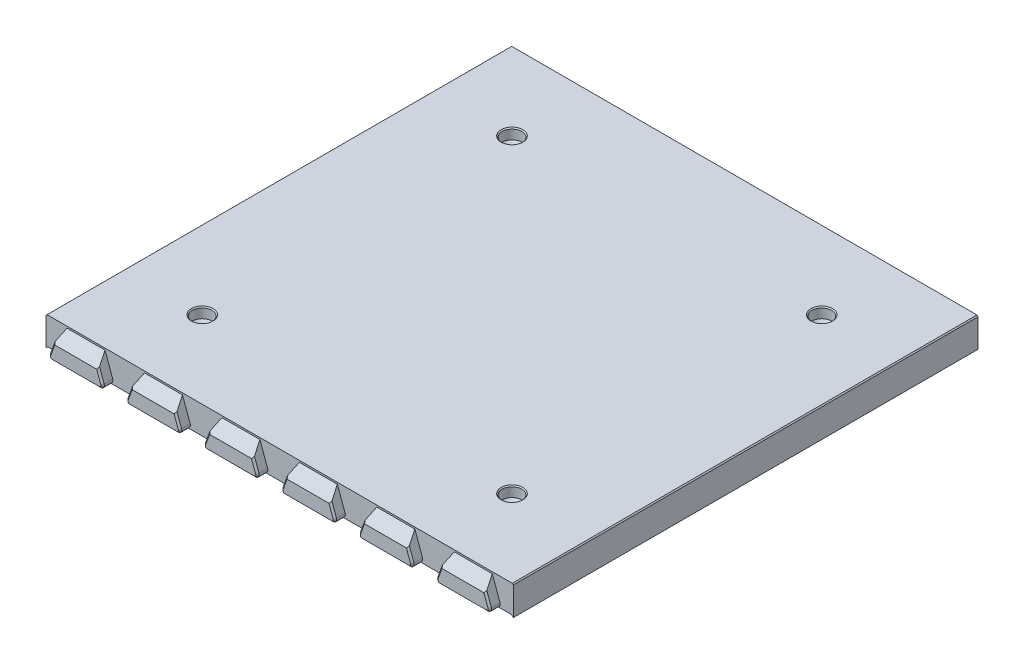
SolidWorks part; units mm, degrees
ref_plane "Front Plane" through (0, 0, 0) normal (0, 0, 1) x (1, 0, 0)
ref_plane "Top Plane" through (0, 0, 0) normal (0, 1, 0) x (1, 0, 0)
ref_plane "Right Plane" through (0, 0, 0) normal (1, 0, 0) x (0, 0, -1)
sketch "Sketch1" plane through (0, 0, 0) normal (0, 0, 1) x (1, 0, 0)
  line L0 (0, 0) -> (0, 8) construction
  line L1 (-67.875, 0) -> (0, 0) construction
  line L2 (-67.875, 0) -> (-67.875, 8)
  line L3 (-67.875, 8) -> (67.875, 8)
  line L5 (-67.875, 0) -> (-65.875, 0)
  line L6 (-65.875, 0) -> (-65.875, 6)
  line L7 (-65.875, 6) -> (65.875, 6)
  line L9 (65.875, 0) -> (65.875, 6)
  line L10 (67.875, 0) -> (65.875, 0)
  line L11 (67.875, 0) -> (67.875, 8)
  point P8 (0, 6)
  dimension "D2" = 6
  dimension "D1" = 67.875
  dimension "D3" = 2
  dimension "D4" = 2
extrude "Boss-Extrude1" add sketch "Sketch1" against normal blind 67.5
sketch "Sketch7" plane through (0, 0, 0) normal (0, 0, 1) x (1, 0, 0)
  line L2 (-65.875, 0) -> (65.875, 0)
  line L13 (-65.875, 0) -> (-65.875, 6)
  line L15 (-65.875, 6) -> (65.875, 6)
  line L16 (65.875, 0) -> (65.875, 6)
  line M3 (-65.875, 0) -> (-65.875, 6)
  line M4 (-65.875, 6) -> (65.875, 6)
  line M5 (65.875, 6) -> (65.875, 0)
extrude "Boss-Extrude7" add sketch "Sketch7" against normal blind 1 contours M4 M3 | M5 region at (0, 3, 0)
sketch "Sketch2" plane through (0, 0, 0) normal (0, 0, 1) x (1, 0, 0)
  line L14 (50.9118, 8) -> (48, 0)
  line L15 (67.875, 8) -> (-67.875, 8) construction
  line L16 (-67.875, 0) -> (67.875, 0) construction
  line L17 (48, 0) -> (64.5, 0)
  line L18 (50.9118, 8) -> (61.5882, 8)
  line L19 (-67.875, 0) -> (67.875, 0) construction
  line L21 (61.5882, 8) -> (64.5, 0)
  line L24 (45, 0) -> (45, 8) construction
  line L27 (28.4118, 8) -> (25.5, 0)
  line L28 (28.4118, 8) -> (39.0882, 8)
  line L29 (25.5, 0) -> (42, 0)
  line L30 (39.0882, 8) -> (42, 0)
  line L31 (5.9118, 8) -> (3, 0)
  line L32 (5.9118, 8) -> (16.5882, 8)
  line L33 (3, 0) -> (19.5, 0)
  line L34 (16.5882, 8) -> (19.5, 0)
  line L35 (-16.5882, 8) -> (-19.5, 0)
  line L36 (-16.5882, 8) -> (-5.9118, 8)
  line L37 (-19.5, 0) -> (-3, 0)
  line L38 (-5.9118, 8) -> (-3, 0)
  line L39 (50.9118, 8) -> (28.4118, 8) construction
  line L40 (67.5, 8) -> (67.5, 0) construction
  line L41 (67.875, 0) -> (67.875, 8) construction
  line L42 (-67.5, 8) -> (-67.5, 0) construction
  line L43 (-67.875, 8) -> (-67.875, 0) construction
  line L44 (-39.0882, 8) -> (-42, 0)
  line L45 (-39.0882, 8) -> (-28.4118, 8)
  line L46 (-42, 0) -> (-25.5, 0)
  line L47 (-28.4118, 8) -> (-25.5, 0)
  line L48 (-61.5882, 8) -> (-64.5, 0)
  line L49 (-61.5882, 8) -> (-50.9118, 8)
  line L50 (-64.5, 0) -> (-48, 0)
  line L51 (-50.9118, 8) -> (-48, 0)
  point P22 (56.25, 8)
  point P23 (33.75, 8)
  dimension "D1" = 70
  dimension "D2" = 0.375
  dimension "D3" = 3
  dimension "D4" = 3
  dimension "D5" = 70
  dimension "D7" = 22.5
  dimension "D8" = 22.5
  dimension "D9" = 0.375
  dimension "D10" = 48
  dimension "D11" = 8
  dimension "D6" = 6
extrude "Boss-Extrude4" add sketch "Sketch2" along normal blind 3
sketch "Sketch8" plane through (0, 0, 0) normal (0, -1, 0) x (1, 0, 0)
  line L0 (-67.875, -22.5) -> (67.875, -22.5) construction
  line L1 (-66.35, -24.7417) -> (-62.65, -23.395)
  line L2 (67.875, -67.5) -> (67.875, 0) construction
  line L3 (-67.875, 0) -> (-64.5, 0) construction
  line L4 (-66.5, -24.9559) -> (-66.5, -20.0441) construction
  line L5 (-66.5, -20.0441) -> (-62.5, -21.5) construction
  line L6 (-62.5, -21.5) -> (-62.5, -23.5) construction
  line L7 (-66.5, -67.5) -> (-66.5, -65.0441) construction
  line L8 (-66.5, -65.0441) -> (-62.5, -66.5) construction
  line L9 (-62.5, -66.5) -> (-62.5, -67.5) construction
  line L10 (-65.875, -67.5) -> (65.875, -67.5) construction
  line L11 (-62.5, -67.5) -> (-66.5, -67.5) construction
  line L12 (-66.5, -24.9559) -> (-62.5, -23.5) construction
  line L13 (0, -67.5) -> (0, 0) construction
  line L22 (-62.65, -21.605) -> (-62.65, -23.395)
  line L23 (-67.875, -67.5) -> (-67.875, 0) construction
  line L28 (-67.875, -67.5) -> (-65.875, -67.5) construction
  line L33 (-66.35, -20.2583) -> (-62.65, -21.605)
  line L34 (-66.35, -24.7417) -> (-66.35, -20.2583)
  line L35 (-66.35, -65.2583) -> (-62.65, -66.605)
  line L36 (-62.65, -66.605) -> (-62.65, -67.35)
  line L37 (-62.65, -67.35) -> (-66.35, -67.35) construction
  line L38 (-66.35, -67.35) -> (-66.35, -65.2583)
  line L39 (-66.35, -67.35) -> (-66.35, -67.5)
  line L40 (-66.35, -67.5) -> (-62.65, -67.5)
  line L41 (-62.65, -67.5) -> (-62.65, -67.35)
  line L42 (66.35, -24.7417) -> (66.35, -20.2583)
  line L43 (66.35, -20.2583) -> (62.65, -21.605)
  line L44 (62.65, -21.605) -> (62.65, -23.395)
  line L45 (66.35, -24.7417) -> (62.65, -23.395)
  line L46 (66.35, -67.5) -> (62.65, -67.5)
  line L47 (66.35, -67.35) -> (66.35, -67.5)
  line L48 (66.35, -67.35) -> (66.35, -65.2583)
  line L49 (66.35, -65.2583) -> (62.65, -66.605)
  line L50 (62.65, -66.605) -> (62.65, -67.35)
  line L51 (62.65, -67.5) -> (62.65, -67.35)
  point P19 (-62.5, -22.5)
  dimension "D1" = 22.5
  dimension "D2" = 0.15
  dimension "D3" = 70
  dimension "D4" = 4
  dimension "D5" = 1.375
  dimension "D6" = 4
  dimension "D7" = 70
  dimension "D8" = 1
  dimension "D9" = 1
  dimension "D10" = 0.15
extrude "Boss-Extrude8" add sketch "Sketch8" against normal up to next and the other way blind 2
chamfer "Chamfer4" distance 0.5 angle 45 14 edges at (64.5, -2, -20.9317) (66.35, -2, -22.5) (64.5, -2, -24.0683) (62.65, -2, -22.5) (-64.5, -2, -20.9317) (-62.65, -2, -22.5) (-64.5, -2, -24.0683) (-66.35, -2, -22.5) (-66.35, -2, -66.3792) (-64.5, -2, -65.9317) (-62.65, -2, -67.0525) (62.65, -2, -67.0525) (64.5, -2, -65.9317) (66.35, -2, -66.3792)
fillet "Fillet4" radius 1 12 edges at (64.5, 0, 1.5) (48, 0, 1.5) (42, 0, 1.5) (25.5, 0, 1.5) (19.5, 0, 1.5) (3, 0, 1.5) (-3, 0, 1.5) (-19.5, 0, 1.5) (-25.5, 0, 1.5) (-42, 0, 1.5) (-48, 0, 1.5) (-64.5, 0, 1.5)
chamfer "Chamfer6" distance 0.5 angle 45 30 edges at (49.7001, 4.671, 3) (62.7999, 4.671, 3) (56.25, 0, 3) (-17.7999, 4.671, 3) (-11.25, 0, 3) (-4.7001, 4.671, 3) (4.7001, 4.671, 3) (11.25, 0, 3) (17.7999, 4.671, 3) (27.2001, 4.671, 3) (40.2999, 4.671, 3) (33.75, 0, 3) (-62.7999, 4.671, 3) (-56.25, 0, 3) (-49.7001, 4.671, 3) (-40.2999, 4.671, 3) (-27.2001, 4.671, 3) (-33.75, 0, 3) (-63.891, 0.4264, 3) (-48.609, 0.4264, 3) (-41.391, 0.4264, 3) (-26.109, 0.4264, 3) (-18.891, 0.4264, 3) (-3.609, 0.4264, 3) (3.609, 0.4264, 3) (18.891, 0.4264, 3) (26.109, 0.4264, 3) (41.391, 0.4264, 3) (48.609, 0.4264, 3) (63.891, 0.4264, 3)
fillet "Fillet2" radius 2 23 edges at (0, 6, -1) (-65.875, 3, -1) (65.875, 6, -10.7156) (65.875, 3, -1) (-65.875, 6, -10.7156) (-64.2625, 6, -23.9819) (-65.875, 3, -24.5688) (-64.2625, 6, -21.0181) (62.65, 6, -22.5) (64.2625, 6, -21.0181) (65.875, 3, -20.4312) (65.875, 3, -24.5688) (64.2625, 6, -23.9819) (62.65, 6, -67.0525) (65.875, 3, -65.4312) (64.2625, 6, -66.0181) (65.875, 6, -45) (-62.65, 6, -67.0525) (-64.2625, 6, -66.0181) (-65.875, 3, -65.4312) (-65.875, 6, -45) (-62.65, 6, -22.5) (-65.875, 3, -20.4312)
mirror "Mirror2" about plane through (0, 0, -67.5) normal (0, 0, 1) of "Fillet4", "Boss-Extrude1", "Boss-Extrude7", "Boss-Extrude4", "Boss-Extrude8", "Chamfer4", "Fillet2", "Chamfer6"
sketch "Sketch9" plane through (0, 0, 0) normal (0, 1, 0) x (1, 0, 0)
  line L16 (-45, 22.5) -> (45, 22.5) construction
  line L17 (-67.875, 67.5) -> (67.875, 67.5) construction
  line L20 (67.875, 135) -> (67.875, 0) construction
  line L24 (0, 22.5) -> (0, 67.5) construction
  line L25 (-67.875, 135) -> (-67.875, 0) construction
  circle A0 centre (-45, 22.5) radius 5
  circle A1 centre (45, 22.5) radius 5
  circle A4 centre (45, 112.5) radius 5
  circle A5 centre (-45, 112.5) radius 5
  point P23 (0, 67.5)
  point P24 (0, 67.5)
  dimension "D3" = 10
  dimension "D1" = 45
  dimension "D2" = 90
extrude "Boss-Extrude9" add sketch "Sketch9" along normal up to next
fillet "Fillet3" radius 3 4 edges at (45, 6, -27.5) (-45, 6, -27.5) (45, 6, -117.5) (-45, 6, -117.5)
sketch "Sketch10" plane through (0, 0, 0) normal (0, 1, 0) x (1, 0, 0)
  circle A0 centre (-45, 112.5) radius 1.85
  circle A1 centre (-45, 22.5) radius 1.85
  circle A2 centre (45, 22.5) radius 1.85
  circle A3 centre (45, 112.5) radius 1.85
  circle A4 centre (-45, 22.5) radius 5 construction
  circle A5 centre (45, 22.5) radius 5 construction
  circle A8 centre (-45, 22.5) radius 5 construction
  circle A9 centre (45, 22.5) radius 5 construction
  dimension "D1" = 3.7
extrude "Cut-Extrude2" cut sketch "Sketch10" along normal through all
sketch "Sketch11" plane through (0, 8, 0) normal (0, 1, 0) x (1, 0, 0)
  circle A0 centre (-45, 112.5) radius 2.85
  circle A1 centre (45, 112.5) radius 2.85
  circle A2 centre (45, 22.5) radius 2.85
  circle A3 centre (-45, 22.5) radius 2.85
  dimension "D1" = 5.7
extrude "Cut-Extrude3" cut sketch "Sketch11" against normal blind 3
chamfer "Chamfer7" distance 1 angle 45 4 edges at (45, 5, -110.65) (-45, 5, -110.65) (45, 5, -20.65) (-45, 5, -20.65)
sketch "Sketch12" plane through (0, 0, 0) normal (1, 0, 0) x (0, 0, -1)
  line L0 (0, 7.5) -> (-3, 4.5)
  line L1 (-3, 1.171) -> (-3, 8) construction
  line L2 (-3, 4.5) -> (-3, 7.5)
  line L3 (-3, 7.5) -> (0, 7.5) construction
  line L4 (67.5, 8) -> (67.5, 0) construction
  line L5 (135, 8) -> (0, 8) construction
  line L6 (135, 0) -> (0, 0) construction
  line L8 (138, 4.5) -> (138, 7.5)
  line L9 (135, 7.5) -> (138, 4.5)
  line L10 (0, 0) -> (0, 8) construction
  line L11 (-3, 8) -> (-2.5, 8) construction
  line L12 (-3, 7.5) -> (-3, 8)
  line L13 (-3, 8) -> (0, 8)
  line L14 (0, 8) -> (0, 7.5)
  line L15 (138, 7.5) -> (135, 7.5) construction
  line L16 (135, 8) -> (135, 7.5)
  line L17 (138, 8) -> (135, 8)
  line L18 (138, 7.5) -> (138, 8)
  dimension "D1" = 45
  dimension "D2" = 3
  dimension "D3" = 0.5
extrude "Cut-Extrude4" cut sketch "Sketch12" against normal through all both and the other way through all
sketch "Sketch13" plane through (0, 0, -135) normal (0, 0, -1) x (-1, 0, 0)
  line L0 (-67.375, 0) -> (-67.875, -0.5)
  line L1 (-63.0719, 0) -> (-67.875, 0) construction
  line L2 (-67.875, -0.5) -> (-67.875, 0)
  line L3 (-67.875, 0) -> (-67.375, 0)
  line L4 (0, 0) -> (0, 8) construction
  line L5 (-67.875, 8) -> (67.875, 8) construction
  line L6 (67.875, 0) -> (67.375, 0)
  line L7 (67.875, -0.5) -> (67.875, 0)
  line L8 (67.375, 0) -> (67.875, -0.5)
  dimension "D1" = 0.5
  dimension "D2" = 0.5
extrude "Boss-Extrude10" add sketch "Sketch13" against normal up to surface (135 mm away) up to face at (0, 2.9792, 0)
chamfer "Chamfer8" distance 0.3 angle 45 6 edges at (-67.875, 8, -67.5) (67.875, 8, -67.5) (-45, 8, -19.65) (45, 8, -19.65) (-45, 8, -109.65) (45, 8, -109.65)
